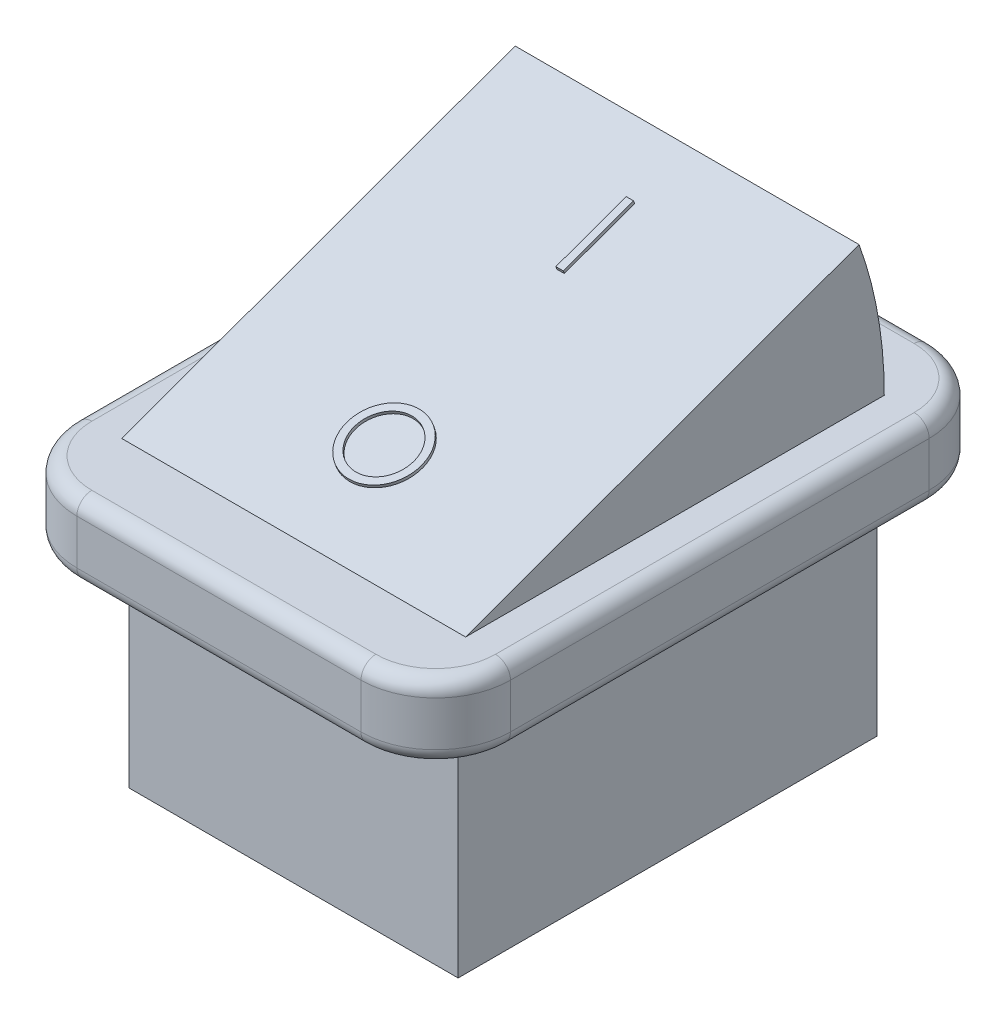
SolidWorks part; units mm, degrees
ref_plane "前视基准面" through (0, 0, 0) normal (0, 0, 1) x (1, 0, 0)
ref_plane "上视基准面" through (0, 0, 0) normal (0, 1, 0) x (1, 0, 0)
ref_plane "右视基准面" through (0, 0, 0) normal (1, 0, 0) x (0, 0, -1)
sketch "草图1" plane through (0, 0, 0) normal (0, 1, 0) x (1, 0, 0)
  line L0 (-11, 14) -> (11, 14)
  line L1 (-11, 14) -> (-11, -14)
  line L2 (11, 14) -> (11, -14)
  line L3 (-11, -14) -> (11, -14)
  line L4 (-11, 14) -> (11, -14) construction
  line L5 (11, 14) -> (-11, -14) construction
  line L6 (-14.5, 19) -> (14.5, 19)
  line L7 (-14.5, 19) -> (-14.5, -19)
  line L8 (14.5, 19) -> (14.5, -19)
  line L9 (-14.5, -19) -> (14.5, -19)
  line L10 (-14.5, 19) -> (14.5, -19) construction
  line L11 (14.5, 19) -> (-14.5, -19) construction
  line L12 (-11, 14) -> (11, 14)
  line L13 (-11, 14) -> (-11, -14)
  line L14 (11, 14) -> (11, -14)
  line L15 (-11, -14) -> (11, -14)
  line L16 (-11, 14) -> (11, -14) construction
  line L17 (11, 14) -> (-11, -14) construction
  point P1 (0, 0)
  point P2 (0, 0)
  point P3 (0, 0)
  dimension "D1" = 22
  dimension "D2" = 28
  dimension "D3" = 29
  dimension "D4" = 38
  dimension "D5" = 22
  dimension "D6" = 28
extrude "凸台-拉伸2" add sketch "草图1" against normal blind 15 contours L1 L3 L2 L0 region at (0, 0, 0)
extrude "凸台-拉伸3" add sketch "草图1<5>" along normal blind 5 contours L7 L9 L8 L6 L3 L1 L0 L2 | L1 L3 L2 L0 region at (0, 0, 0) region at (0, 0, -18.522)
sketch "草图1<5>" plane through (0, 0, 0) normal (0, 1, 0) x (1, 0, 0) same geometry as "草图1"
sketch "草图2" plane through (0, 5, 0) normal (0, 1, 0) x (1, 0, 0)
  line L0 (-11.5, 14) -> (11.5, 14)
  line L1 (-11.5, 14) -> (-11.5, -14)
  line L2 (11.5, 14) -> (11.5, -14)
  line L3 (-11.5, -14) -> (11.5, -14)
  line L4 (-11.5, 14) -> (11.5, -14) construction
  line L5 (11.5, 14) -> (-11.5, -14) construction
  point P1 (0, 0)
  dimension "D1" = 23
  dimension "D2" = 28
revolve "旋转1" add sketch "草图2" angle 20 about L3
sketch "草图3" plane through (0, 8.9146, 3.2447) normal (0, 0.9397, 0.342) x (1, 0, 0)
  line L0 (-11.5, 16.5544) -> (11.5, -11.4456)
  line L1 (11.5, 16.5544) -> (-11.5, -11.4456)
  line L2 (0, 10.0544) -> (0, -4.9456)
  line L3 (0.25, 12.5544) -> (0.25, 7.5544)
  line L4 (0.25, 12.5544) -> (-0.25, 12.5544)
  line L5 (0.25, 7.5544) -> (-0.25, 7.5544)
  line L6 (-0.25, 12.5544) -> (-0.25, 7.5544)
  line L7 (0.25, 12.5544) -> (-0.25, 7.5544) construction
  line L8 (0.25, 7.5544) -> (-0.25, 12.5544) construction
  circle A0 centre (0, -4.9456) radius 2.5
  circle A1 centre (0, -4.9456) radius 2
  point P12 (0, 2.5544)
  dimension "D1" = 5
  dimension "D2" = 4
  dimension "D3" = 5
  dimension "D4" = 0.5
extrude "凸台-拉伸4" add sketch "草图3" along normal blind 0.2 contours L4 L6 L5 L3 | A1 A0 region at (1.7178, 7.8106, 6.2778) region at (-0.125, 11.5156, -3.9014)
fillet "圆角1" radius 5 4 edges at (-14.5, 2.5, -19) (14.5, 2.5, -19) (14.5, 2.5, 19) (-14.5, 2.5, 19)
fillet "圆角2" radius 1 16 edges at (13.0355, 0, -17.5355) (0, 0, -19) (-13.0355, 0, -17.5355) (-14.5, 0, 0) (-13.0355, 0, 17.5355) (0, 0, 19) (13.0355, 0, 17.5355) (13.0355, 5, -17.5355) (0, 5, -19) (-13.0355, 5, -17.5355) (-14.5, 5, 0) (-13.0355, 5, 17.5355) (0, 5, 19) (13.0355, 5, 17.5355) (14.5, 0, 0) (14.5, 5, 0)
